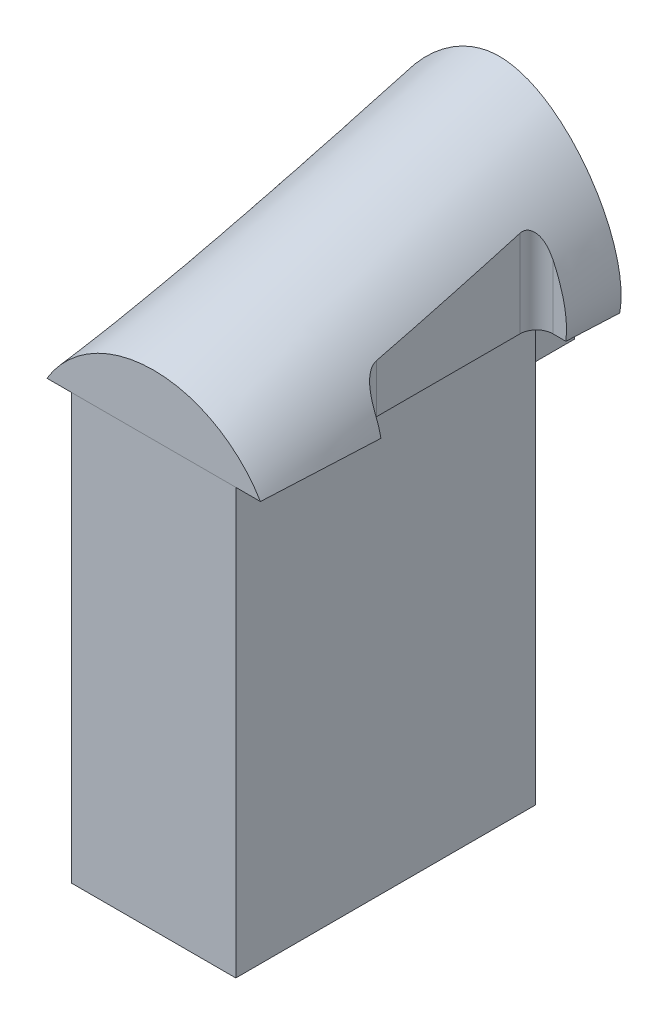
SolidWorks part; units mm, degrees
ref_plane "前视基准面" through (0, 0, 0) normal (0, 0, 1) x (1, 0, 0)
ref_plane "上视基准面" through (0, 0, 0) normal (0, 1, 0) x (1, 0, 0)
ref_plane "右视基准面" through (0, 0, 0) normal (1, 0, 0) x (0, 0, -1)
other "质心 (COM)"
sketch "草图1" plane through (0, 0, 0) normal (0, 1, 0) x (1, 0, 0)
  line L1 (-20, -36.5) -> (20, -36.5)
  line L2 (-20, -36.5) -> (-20, 36.5)
  line L3 (-20, 36.5) -> (20, 36.5)
  line L4 (20, -36.5) -> (20, 36.5)
  line L5 (-20, -36.5) -> (20, 36.5) construction
  line L6 (-20, 36.5) -> (20, -36.5) construction
  point P0 (0, 0)
  dimension "D1" = 40
  dimension "D2" = 73
extrude "凸台-拉伸1" add sketch "草图1" along normal mid plane 103.5
sketch "草图2" plane through (0, 0, -36.5) normal (0, 0, -1) x (-1, 0, 0)
  line L0 (-20, 51.75) -> (-20, -51.75) construction
  line L1 (-19, 51.75) -> (7.5, 51.75)
  line L2 (-19, 51.75) -> (-19, 40.75)
  line L3 (-19, 40.75) -> (7.5, 40.75)
  line L4 (7.5, 51.75) -> (7.5, 40.75)
  dimension "D1" = 11
  dimension "D2" = 26.5
  dimension "D3" = 1
extrude "凸台-拉伸2" add sketch "草图2" along normal blind 10.5
sketch "草图3" plane through (0, 0, -47) normal (0, 0, -1) x (-1, 0, 0)
  line L0 (-30, 51.75) -> (30, 51.75)
  line L2 (-20, -51.75) -> (20, -51.75) construction
  spline S0 degree 3 poles (-30, 51.75) (-32.9608, 67.553) (-0.1223, 116.2579) (33.0721, 64.9367) (30, 51.75) knots 0 0 0 0 0.500505 1 1 1 1
  point P4 (0, 51.75)
  point P12 (-16.8524, 83.8663)
  dimension "D1" = 60
  dimension "D2" = 143
sketch "草图4" plane through (0, 0, 36.5) normal (0, 0, 1) x (1, 0, 0)
  line L0 (-26, 51.75) -> (26, 51.75)
  line L1 (30, 51.75) -> (-30, 51.75) construction
  arc A0 (-26, 51.75) -> (26, 51.75) centre (0, 36.1214) cw
  point P4 (0, 51.75)
  dimension "D1" = 52
loft "放样1" add profiles "草图3", "草图4" connector at (30, 51.75, -47) connector at (26, 51.75, 36.5)
sketch "草图5" plane through (0, 51.75, 0) normal (0, -1, 0) x (1, 0, 0)
  line L0 (0, 13.4118) -> (0, -19.6269) construction
  line L1 (-27.3413, 8.5) -> (-26.243, 8.5)
  line L3 (-22.243, 4.5) -> (-22.243, -30.5)
  line L4 (-26.243, -34.5) -> (-29.4012, -34.5)
  line L5 (-29.4012, -34.5) -> (-36.9893, -34.5)
  line L6 (-26, 36.5) -> (26, 36.5) construction
  line L7 (36.9893, 9.3475) -> (27.3413, 8.5)
  line L8 (36.9893, -34.5) -> (36.9893, 9.3475)
  line L9 (29.4012, -34.5) -> (36.9893, -34.5)
  line L10 (26.243, -34.5) -> (29.4012, -34.5)
  line L12 (-36.9893, -34.5) -> (-36.9893, 9.3475)
  line L13 (-36.9893, 9.3475) -> (-27.3413, 8.5)
  line L14 (22.243, 4.5) -> (22.243, -30.5)
  line L15 (27.3413, 8.5) -> (26.243, 8.5)
  arc A0 (-22.243, -30.5) -> (-26.243, -34.5) centre (-26.243, -30.5) cw
  arc A1 (-22.243, 4.5) -> (-26.243, 8.5) centre (-26.243, 4.5) ccw
  arc A2 (22.243, 4.5) -> (26.243, 8.5) centre (26.243, 4.5) cw
  arc A3 (22.243, -30.5) -> (26.243, -34.5) centre (26.243, -30.5) ccw
  dimension "D3" = 4
  dimension "D1" = 28
  dimension "D2" = 71
extrude "切除-拉伸1" cut sketch "草图5" against normal through all
